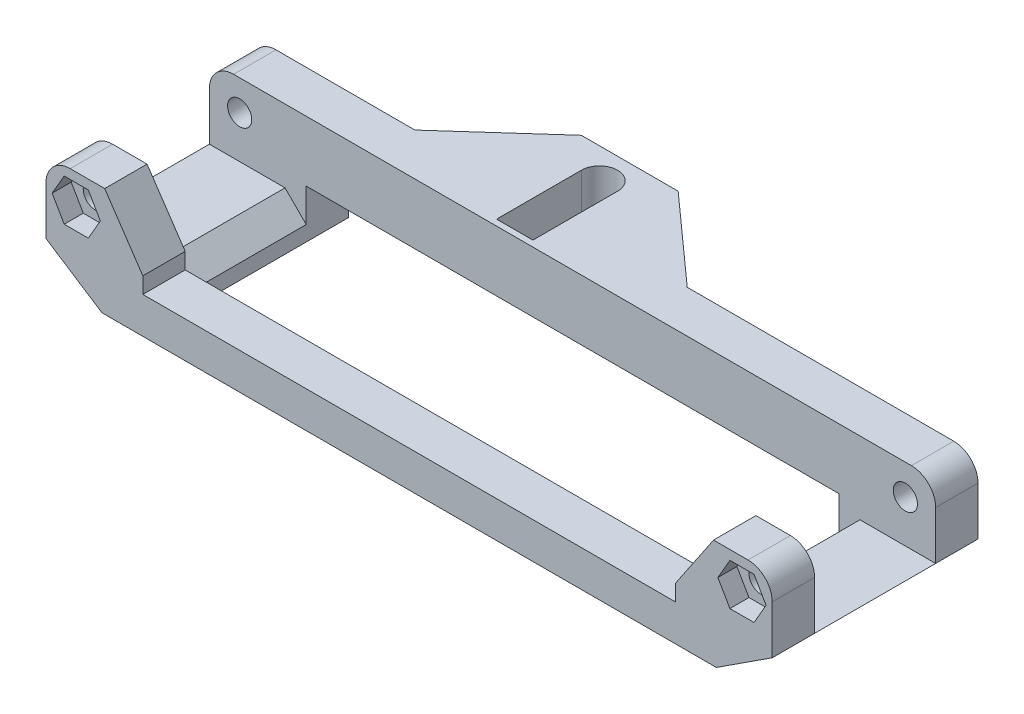
SolidWorks part; units mm, degrees
ref_plane "Front Plane" through (0, 0, 0) normal (0, 0, 1) x (1, 0, 0)
ref_plane "Top Plane" through (0, 0, 0) normal (0, 1, 0) x (1, 0, 0)
ref_plane "Right Plane" through (0, 0, 0) normal (1, 0, 0) x (0, 0, -1)
sketch "Sketch1" plane through (0, 0, 0) normal (0, 1, 0) x (1, 0, 0)
  line L0 (-60, 17) -> (-60, 10)
  line L1 (-60, 10) -> (-28, 10)
  line L2 (-28, 10) -> (-28, -10)
  line L3 (-28, 0) -> (-20, 0)
  line L4 (-20, -10) -> (-20, 10)
  line L5 (-20, 10) -> (20, 10)
  line L6 (20, 10) -> (20, -10)
  line L7 (20, 0) -> (28, 0)
  line L8 (28, -10) -> (28, 10)
  line L9 (28, 10) -> (60, 10)
  line L10 (60, 10) -> (60, 17)
  line L11 (60, 17) -> (-60, 17)
  line L12 (60, -17) -> (-60, -17)
  line L13 (60, -10) -> (60, -17)
  line L14 (28, -10) -> (60, -10)
  line L15 (-20, -10) -> (20, -10)
  line L16 (-60, -10) -> (-28, -10)
  line L17 (-60, -17) -> (-60, -10)
  line L18 (-51, -10) -> (-43.7206, 10)
  line L19 (-36.7206, 10) -> (-44, -10)
  line L20 (0, 24.9869) -> (0, -25.8896) construction
  line L21 (51, -10) -> (43.7206, 10)
  line L22 (36.7206, 10) -> (44, -10)
  line L23 (-44, -10) -> (-44, -17)
  line L24 (44, -10) -> (44, -17)
  line L25 (-28, 10) -> (-20, 10)
  line L26 (20, 10) -> (28, 10)
  point P0 (0, 10)
  point P16 (0, 17)
  dimension "D1" = 40
  dimension "D2" = 120
  dimension "D3" = 8
  dimension "D4" = 8
  dimension "D5" = 10
  dimension "D6" = 7
  dimension "D7" = 9
  dimension "D8" = 7
  dimension "D9" = 70
extrude "Boss-Extrude1" add sketch "Sketch1" along normal blind 10 contours L20 L11 L0 L1 L25 L5 | L11 L20 L5 L26 L9 L10 | L14 L24 L12 L13 | L23 L16 L17 L12
fillet "Fillet4" radius 4 2 edges at (60, 10, -13.5) (-60, 10, -13.5)
sketch "Sketch8" plane through (0, 0, 0) normal (0, -1, 0) x (1, 0, 0)
  line L0 (0, -7.4767) -> (0, 7.4767) construction
  line L1 (11.9672, 0) -> (-11.9672, 0) construction
  line L2 (-44, 17) -> (-44, 10)
  line L3 (-60, 17) -> (-44, 17)
  line L4 (-60, 10) -> (-60, 17)
  line L5 (-44, 10) -> (-60, 10)
  line L6 (44, 10) -> (60, 10)
  line L7 (60, 10) -> (60, 17)
  line L8 (60, 17) -> (44, 17)
  line L9 (44, 17) -> (44, 10)
  line L10 (44, 10) -> (60, 10)
  line L11 (60, 10) -> (60, 17)
  line L12 (60, 17) -> (44, 17)
  line L13 (44, 17) -> (44, 10)
  line L14 (44, -17) -> (44, -10)
  line L15 (60, -17) -> (44, -17)
  line L16 (60, -10) -> (60, -17)
  line L17 (44, -10) -> (60, -10)
  line L18 (-60, -17) -> (-44, -17)
  line L19 (-60, -10) -> (-60, -17)
  line L20 (-44, -10) -> (-60, -10)
  line L21 (-44, -17) -> (-44, -10)
  dimension "D1" = 0
extrude "Boss-Extrude3" add sketch "Sketch8" along normal blind 2
sketch "Sketch9" plane through (0, -2, 0) normal (0, -1, 0) x (1, 0, 0)
  line L0 (60, -17) -> (60, 17)
  line L1 (60, -17) -> (60, -10) construction
  line L2 (44, -17) -> (60, -17) construction
  line L3 (60, 17) -> (44, 17)
  line L4 (44, 17) -> (44, 10) construction
  line L5 (44, 17) -> (44, -17)
  line L6 (44, -10) -> (44, -17) construction
  line L7 (44, -17) -> (60, -17)
  line L8 (-44, -17) -> (-44, 17)
  line L9 (-60, -17) -> (-44, -17) construction
  line L10 (-44, -17) -> (-44, -10) construction
  line L11 (-44, 10) -> (-44, 17) construction
  line L12 (-44, 17) -> (-60, 17)
  line L13 (-44, 17) -> (-60, 17) construction
  line L14 (-60, 17) -> (-60, 10) construction
  line L15 (-60, 17) -> (-60, -17)
  line L16 (-60, -10) -> (-60, -17) construction
  line L17 (-60, -17) -> (-44, -17)
  line L18 (60, 17) -> (44, 17) construction
extrude "Boss-Extrude4" add sketch "Sketch9" along normal blind 6 contours L15 L17 L8 L12 | L7 L0 L3 L5
sketch "Sketch10" plane through (0, 10, 0) normal (0, 1, 0) x (1, 0, 0)
  line L0 (-33.0454, 17) -> (-18.5454, 30)
  line L1 (56, 17) -> (-56, 17) construction
  line L2 (-18.5454, 30) -> (-2.5454, 30)
  line L3 (-2.5454, 30) -> (11.9546, 17)
  line L4 (-33.0454, 17) -> (11.9546, 17)
  point P4 (-10.5454, 30)
  dimension "D1" = 13
  dimension "D2" = 45
  dimension "D3" = 16
extrude "Boss-Extrude5" add sketch "Sketch10" against normal up to surface (10 mm away) up to face at (0, 0, -13.5)
sketch "Sketch11" plane through (0, 10, 0) normal (0, 1, 0) x (1, 0, 0)
  line L0 (-10.5454, 25) -> (-10.5454, 11) construction
  line L2 (-7.5454, 25) -> (-7.5454, 11)
  line L3 (-13.5454, 25) -> (-13.5454, 11)
  line L4 (-2.5454, 30) -> (-18.5454, 30) construction
  line L5 (-56, 10) -> (56, 10) construction
  arc A0 (-7.5454, 25) -> (-13.5454, 25) centre (-10.5454, 25) ccw
  arc A1 (-13.5454, 11) -> (-7.5454, 11) centre (-10.5454, 11) ccw
  point P4 (-10.5454, 18)
  point P11 (-10.5454, 30)
  dimension "D1" = 3
  dimension "D2" = 14
  dimension "D3" = 1
extrude "Cut-Extrude3" cut sketch "Sketch11" against normal up to surface (10 mm away) up to face at (-5.2727, 0, -18.5)
chamfer "Chamfer1" distance 6 angle 57 2 edges at (-60, -8, 0) (60, -8, 0)
sketch "Sketch13" plane through (44, 0, 0) normal (-1, 0, 0) x (0, 0, 1)
  line L0 (10, -2) -> (17, -2)
  line L1 (10, -2) -> (-10, -2) construction
  line L2 (10, 10) -> (10, -2) construction
  line L3 (17, -8) -> (17, 10) construction
  line L4 (17, -2) -> (17, -8)
  line L5 (17, -8) -> (-17, -8) construction
  line L6 (17, -8) -> (10, -8)
  line L7 (10, -8) -> (10, -2)
extrude "Boss-Extrude6" add sketch "Sketch13" along direction (-1, 0, 0) on the side of the normal up to surface (88 mm away) contours L7 L0 L4 L6
chamfer "Chamfer2" distance 3.5 2 edges at (44, -2, 0) (-44, -2, 0)
sketch "Sketch14" plane through (0, 0, -17) normal (0, 0, -1) x (-1, 0, 0)
  point P0 (-55, 5)
  point P1 (55, 5)
hole_wizard "CSK for M4 Flat Head Machine Screw1" positions "Sketch15" profile "Sketch16" countersink size "M4" standard "ANSI Metric"
sketch "Sketch15" plane through (0, 0, -17) normal (0, 0, -1) x (-1, 0, 0)
  point P0 (-55, 5)
  point P2 (55, 5)
sketch "Sketch16" plane through (55, 5, -17) normal (1, 0, 0) x (0, 1, 0)
  line L0 (0, 0) -> (0, 55)
  line L1 (0, 55) -> (2, 53.7983)
  line L2 (2, 53.7983) -> (2, 1.8)
  line L3 (2, 1.8) -> (3.8, 0)
  line L5 (3.8, 0) -> (0, 0)
  line L6 (-2, 1.8) -> (-3.8, 0) construction
  line L10 (0, 55) -> (-2, 53.7983) construction
  line L11 (0, -6.35) -> (0, 107.95) construction
  dimension "Hole Dia." = 4
  dimension "Hole Depth" = 55
  dimension "Near C'Sink Dia." = 7.6
  dimension "Near C'Sink Angle" = 90
  dimension "Drill Angle" = 118
fillet "Fillet5" radius 4 2 edges at (-60, 10, 13.5) (60, 10, 13.5)
sketch "Sketch17" plane through (0, 10, 0) normal (0, 1, 0) x (1, 0, 0)
  line L0 (-13.5454, 11) -> (-13.5454, 10)
  line L1 (-56, 10) -> (-13.3739, 10) construction
  line L2 (-13.5454, 10) -> (-7.5454, 10)
  line L3 (-7.717, 10) -> (56, 10) construction
  line L4 (-7.5454, 10) -> (-7.5454, 11)
  line L5 (-7.5454, 11) -> (-13.5454, 11)
  arc A0 (-13.5454, 11) -> (-13.3739, 10) centre (-10.5454, 11) ccw construction
  arc A1 (-7.717, 10) -> (-7.5454, 11) centre (-10.5454, 11) ccw construction
  dimension "D1" = 1
extrude "Boss-Extrude7" add sketch "Sketch17" against normal up to surface (10 mm away) up to face at (-7.5324, 0, -17.3561)
sketch "Sketch18" plane through (0, 0, 17) normal (0, 0, 1) x (1, 0, 0)
  line L0 (-44, 10) -> (-56, 10) construction
  line L1 (51.0163, 5) -> (53.0081, 1.55)
  line L2 (53.0081, 1.55) -> (56.9919, 1.55)
  line L3 (56.9919, 1.55) -> (58.9837, 5)
  line L4 (58.9837, 5) -> (56.9919, 8.45)
  line L5 (56.9919, 8.45) -> (53.0081, 8.45)
  line L6 (53.0081, 8.45) -> (51.0163, 5)
  line L7 (-51.0163, 5) -> (-53.0081, 8.45)
  line L8 (-53.0081, 8.45) -> (-56.9919, 8.45)
  line L9 (-56.9919, 8.45) -> (-58.9837, 5)
  line L10 (-58.9837, 5) -> (-56.9919, 1.55)
  line L11 (-56.9919, 1.55) -> (-53.0081, 1.55)
  line L12 (-53.0081, 1.55) -> (-51.0163, 5)
  line L15 (56, 10) -> (44, 10) construction
  circle A0 centre (55, 5) radius 3.45 construction
  circle A1 centre (-55, 5) radius 3.45 construction
  dimension "D1" = 6.9
  dimension "D2" = 6.9
extrude "Cut-Extrude4" cut sketch "Sketch18" against normal blind 3.15
chamfer "Chamfer3" distance 6.3 angle 56 2 edges at (44, 10, 13.5) (-44, 10, 13.5)
